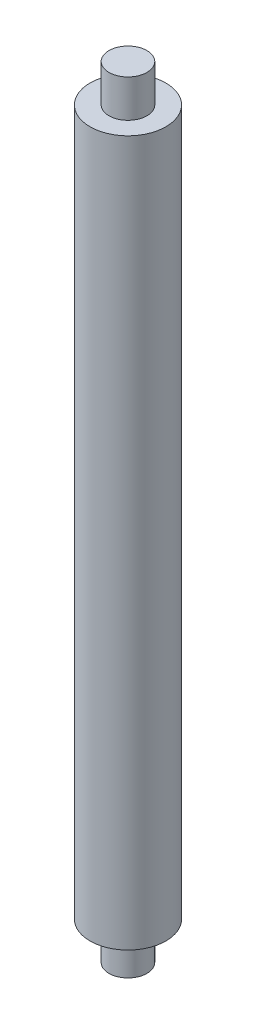
SolidWorks part; units mm, degrees
material "6061 Alloy"
ref_plane "Front Plane" through (0, 0, 0) normal (0, 0, 1) x (1, 0, 0)
ref_plane "Top Plane" through (0, 0, 0) normal (0, 1, 0) x (1, 0, 0)
ref_plane "Right Plane" through (0, 0, 0) normal (1, 0, 0) x (0, 0, -1)
sketch "Sketch1" plane through (0, 0, 0) normal (0, 1, 0) x (1, 0, 0)
  circle A0 centre (0, 0) radius 5
  dimension "D1" = 10
extrude "Boss-Extrude1" add sketch "Sketch1" along normal blind 92.964
sketch "Sketch2" plane through (0, 92.964, 0) normal (0, 1, 0) x (1, 0, 0)
  circle A0 centre (0, 0) radius 2.5
  dimension "D1" = 5
extrude "Boss-Extrude2" add sketch "Sketch2" along normal blind 4.953 contours A0 region at (0, 92.964, 0)
sketch "Sketch3" plane through (0, 0, 0) normal (0, -1, 0) x (1, 0, 0)
  circle A0 centre (0, 0) radius 2.5
  dimension "D1" = 5
extrude "Boss-Extrude3" add sketch "Sketch3" along normal blind 4.953
